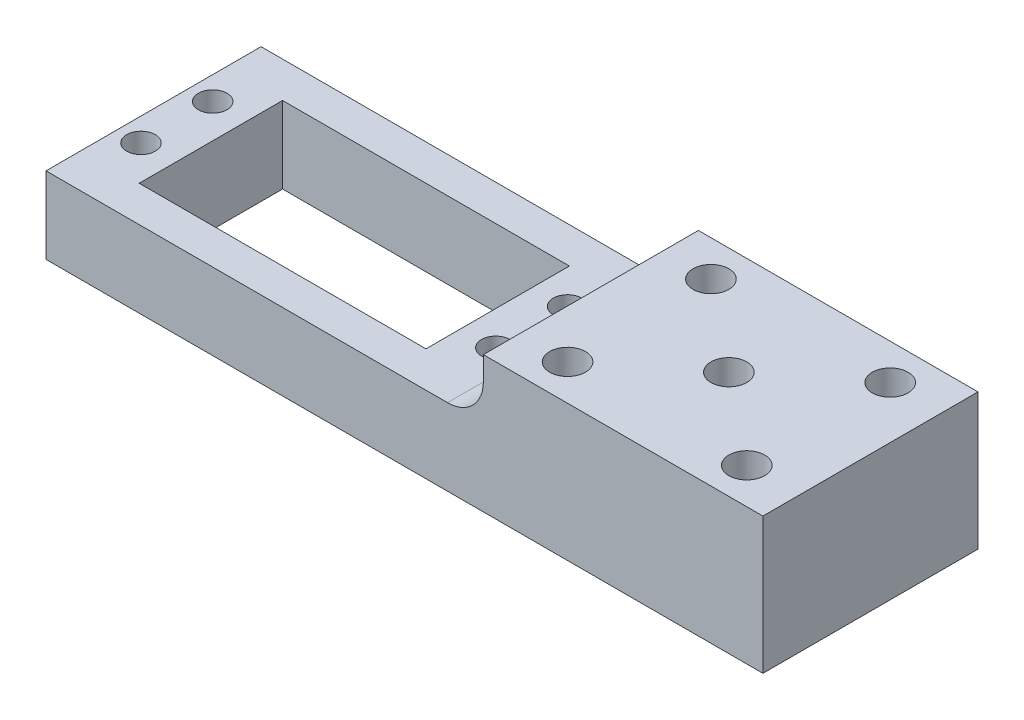
SolidWorks part; units mm, degrees
note: The reader was unsure of these and kept them because the rebuilt part matched: shared geometry of "Sketch1<4>".
material "ABS"
ref_plane "Front Plane" through (0, 0, 0) normal (0, 0, 1) x (1, 0, 0)
ref_plane "Top Plane" through (0, 0, 0) normal (0, 1, 0) x (1, 0, 0)
ref_plane "Right Plane" through (0, 0, 0) normal (1, 0, 0) x (0, 0, -1)
sketch "Sketch1" plane through (0, 0, 0) normal (0, 1, 0) x (1, 0, 0)
  line L0 (-31.2167, 0) -> (31.2167, 0) construction
  line L1 (-20, 10) -> (20, 10)
  line L2 (-20, 10) -> (-20, -10)
  line L3 (-20, -10) -> (20, -10)
  line L4 (20, 10) -> (20, -10)
  line L5 (-20, 10) -> (20, -10) construction
  line L6 (-20, -10) -> (20, 10) construction
  line L7 (0, 15) -> (28, 15)
  line L8 (-28, 0) -> (-28, -15)
  line L9 (-28, -15) -> (0, -15)
  line L11 (-28, 15) -> (28, -15) construction
  line L12 (-28, -15) -> (28, 15) construction
  line L13 (0, 0) -> (0, -22.8648) construction
  line L18 (-28, 15) -> (-28, -15)
  line L19 (-28, 15) -> (72, 15)
  line L20 (-28, -15) -> (72, -15)
  line L21 (72, 15) -> (72, -15)
  line L22 (33, 15) -> (33, -15)
  circle A0 centre (24.75, 5) radius 2
  circle A1 centre (24.75, -5) radius 2
  circle A2 centre (-24.75, -5) radius 2
  circle A3 centre (-24.75, 5) radius 2
  point P0 (0, 0)
  point P6 (0, 0)
  point P14 (0, 0)
extrude "Boss-Extrude1" add sketch "Sketch1" along normal blind 10.7
extrude "Boss-Extrude2" add sketch "Sketch1<4>" along normal blind 19
sketch "Sketch1<4>" plane through (0, 0, 0) normal (0, 1, 0) x (1, 0, 0) same geometry as "Sketch1"
fillet "Fillet1" radius 5 1 edges at (33, 10.7, 0)
sketch "Sketch2" plane through (0, 0, 0) normal (0, -1, 0) x (1, 0, 0)
  circle A0 centre (52.25, 0) radius 2.5
  circle A4 centre (39.75, 10) radius 2.5
  circle A5 centre (39.75, -10) radius 2.5
  circle A6 centre (64.75, -10) radius 2.5
  circle A7 centre (64.75, 10) radius 2.5
extrude "Cut-Extrude2" cut sketch "Sketch2" against normal up to next
